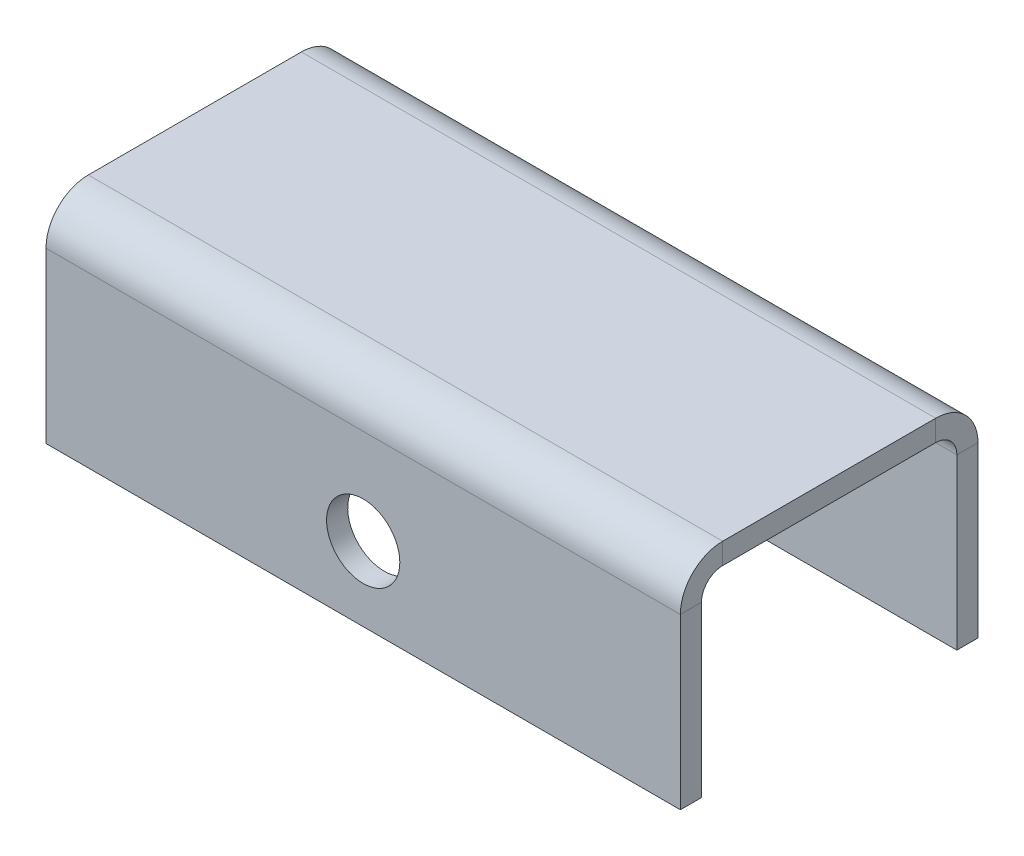
SolidWorks part; units mm, degrees
note: The reader was unsure of these and kept them because the rebuilt part matched: flange length of "Edge-Flange1"; thickness of "Edge-Flange1".
ref_plane "Front Plane" through (0, 0, 0) normal (0, 0, 1) x (1, 0, 0)
ref_plane "Top Plane" through (0, 0, 0) normal (0, 1, 0) x (1, 0, 0)
ref_plane "Right Plane" through (0, 0, 0) normal (1, 0, 0) x (0, 0, -1)
sketch "Sketch1" plane through (0, 0, 0) normal (0, 1, 0) x (1, 0, 0)
  line L1 (-0.9529, 0.4926) -> (75.2471, 0.4926)
  line L2 (-0.9529, 0.4926) -> (-0.9529, -35.2574)
  line L3 (-0.9529, -35.2574) -> (75.2471, -35.2574)
  line L4 (75.2471, 0.4926) -> (75.2471, -35.2574)
  dimension "D1" = 76.2
  dimension "D2" = 35.75
base flange "Base-Flange1" sketch "Sketch1" thickness 2.54 reverse thickness direction no parameters "D1"=2.54
edge flange "Edge-Flange1" sketch "Sketch8" flange profiles "Sketch8", "Sketch10" flange angle 90 flange length 25.4 flange position material inside bend radius 2.54 thickness 2.54 relief rectangular parameters "D1"=3.335, "D6"=10, "D8"=1
sketch "Sketch8" plane through (0, -2.54, 35.2574) normal (0, 0, 1) x (-1, 0, 0)
  line L2 (-75.2471, 0) -> (-75.2471, 22.86)
  line L3 (-75.2471, 22.86) -> (0.9529, 22.86)
  line L4 (0.9529, 22.86) -> (0.9529, 0)
  line L15 (0.9529, 0) -> (-75.2471, 0) construction
  line L16 (0.9529, 0) -> (-75.2471, 0)
sketch "Sketch10" plane through (0, -2.54, -0.4926) normal (0, 0, -1) x (1, 0, 0)
  line L0 (75.2471, 0) -> (-0.9529, 0) construction
  line L1 (75.2471, 0) -> (-0.9529, 0)
  line L2 (-0.9529, 0) -> (-0.9529, 22.86)
  line L3 (-0.9529, 22.86) -> (75.2471, 22.86)
  line L4 (75.2471, 22.86) -> (75.2471, 0)
bend "EdgeBend1" bend radius 2.54 bend angle 90 parameters "D5"=1
bend "EdgeBend2" bend radius 2.54 bend angle 90 parameters "D5"=3
hole_wizard "Tap Drill for M10x1.25 Tap1" positions "Sketch11" profile "Sketch12" hole size "M10x1.25" standard "ANSI Metric"
sketch "Sketch11" plane through (0, 0, 35.2574) normal (0, 0, 1) x (1, 0, 0)
  line L0 (-0.9529, -5.08) -> (-0.9529, -25.4) construction
  line L1 (-0.9529, 0) -> (75.2471, 0) construction
  point P0 (37.1471, -16.51)
  dimension "D1" = 38.1
  dimension "D2" = 16.51
sketch "Sketch12" plane through (37.1471, -16.51, 35.2574) normal (1, 0, 0) x (0, -1, 0)
  line L0 (0, 0) -> (0, 38.3938)
  line L1 (0, 38.3938) -> (4.4, 35.75)
  line L2 (4.4, 35.75) -> (4.4, 0)
  line L5 (4.4, 0) -> (0, 0)
  line L10 (0, 38.3938) -> (-4.4, 35.75) construction
  line L11 (0, -6.35) -> (0, 107.95) construction
  dimension "Hole Dia." = 8.8
  dimension "Hole Depth" = 35.75
  dimension "Drill Angle" = 118
sketch "Sketch13" plane through (-0.9529, 0, 0) normal (-1, 0, 0) x (0, 0, 1)
  line L0 (2.0474, -25.4) -> (2.0474, -5.08) construction
  line L1 (-0.4926, -25.4) -> (2.0474, -25.4) construction
  point P0 (2.0474, -12.7)
  dimension "D1" = 12.7
sketch "Sketch14" plane through (-0.9529, 0, 0) normal (-1, 0, 0) x (0, 0, 1)
  line L0 (-0.4926, -25.4) -> (-0.4926, -5.08) construction
  point P0 (-0.4926, -12.7)
sketch "Bend-Lines1" [suppressed] plane through (0, 0, 0) normal (0, 1, 0) x (1, 0, 0)
sketch "Bounding-Box1" [suppressed] plane through (0, 0, 0) normal (0, 1, 0) x (1, 0, 0)
sheet metal parameters "Sheet-Metal1" thickness 2.54 parameters "D1"=2.54
flat pattern "Flat-Pattern1" [suppressed]
sketch "Bend-Lines2" plane through (0, 0, 0) normal (0, 1, 0) x (1, 0, 0)
sketch3d "Bounding-Box2" [suppressed]
  line L0 (-49.8471, -33.2574, 0) -> (0.9529, -33.2574, 0) construction
  line L1 (-49.8471, 0.4926, 0) -> (0.9529, 0.4926, 0) construction
  line L2 (-49.8471, -33.2574, 0) -> (-49.8471, 0.4926, 0) construction
  line L3 (0.9529, -33.2574, 0) -> (0.9529, 0.4926, 0) construction
sheet metal parameters "Sheet-Metal2" thickness 2.54 parameters "D1"=2.54, "D7"=3.175
flat pattern "Flat-Pattern1"
sketch "Bend-Lines2" plane through (0, 0, 0) normal (0, 1, 0) x (1, 0, 0)
  line L0 (-0.9529, -30.6135) -> (49.8471, -30.6135) construction
  line L1 (-0.9529, -30.6135) -> (49.8471, -30.6135) construction
  line L2 (49.8471, -2.1512) -> (-0.9529, -2.1512) construction
  line L3 (49.8471, -2.1512) -> (-0.9529, -2.1512) construction
sketch3d "Bounding-Box2" [suppressed]
  line L0 (-0.9529, 20.6049, 0) -> (-0.9529, -53.3696, 0) construction
  line L1 (49.8471, 20.6049, 0) -> (49.8471, -53.3696, 0) construction
  line L2 (-0.9529, 20.6049, 0) -> (49.8471, 20.6049, 0) construction
  line L3 (-0.9529, -53.3696, 0) -> (49.8471, -53.3696, 0) construction
bend of the flat pattern "Flatten-<EdgeBend1>1"
bend of the flat pattern "Flatten-<EdgeBend2>1"
sheet metal parameters "Sheet-Metal3" thickness 2.54 parameters "D1"=2.54, "D7"=3.175
flat pattern "Flat-Pattern1"
sketch "Bend-Lines2" plane through (0, 0, 0) normal (0, 1, 0) x (1, 0, 0)
  line L0 (-0.9529, -33.1697) -> (75.2471, -33.1697) construction
  line L1 (-0.9529, -33.1697) -> (75.2471, -33.1697) construction
  line L2 (75.2471, -1.595) -> (-0.9529, -1.595) construction
  line L3 (75.2471, -1.595) -> (-0.9529, -1.595) construction
sketch3d "Bounding-Box2" [suppressed]
  line L0 (-0.9529, 21.7174, 0) -> (-0.9529, -56.4821, 0) construction
  line L1 (75.2471, 21.7174, 0) -> (75.2471, -56.4821, 0) construction
  line L2 (-0.9529, 21.7174, 0) -> (75.2471, 21.7174, 0) construction
  line L3 (-0.9529, -56.4821, 0) -> (75.2471, -56.4821, 0) construction
bend of the flat pattern "Flatten-<EdgeBend1>1"
bend of the flat pattern "Flatten-<EdgeBend2>1"
